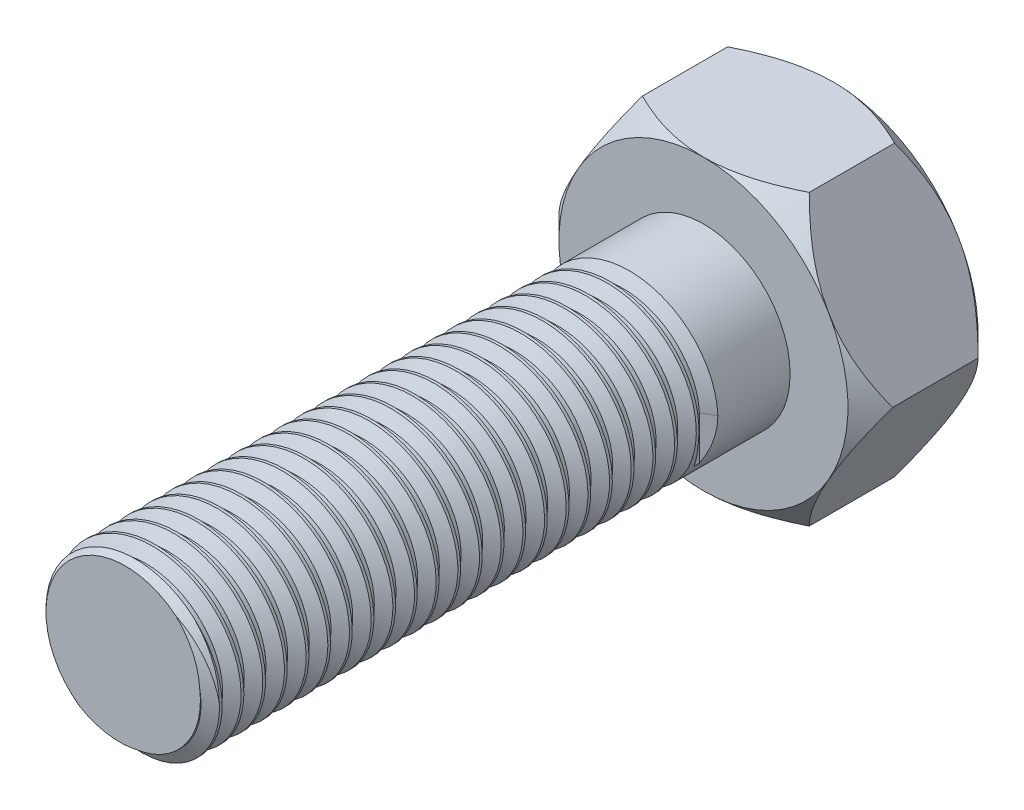
SolidWorks part; units mm, degrees
ref_plane "Front Plane" through (0, 0, 0) normal (0, 0, 1) x (1, 0, 0)
ref_plane "Top Plane" through (0, 0, 0) normal (0, 1, 0) x (1, 0, 0)
ref_plane "Right Plane" through (0, 0, 0) normal (1, 0, 0) x (0, 0, -1)
sketch "Sketch1" plane through (0, 0, 0) normal (0, 0, 1) x (1, 0, 0)
  line L1 (5.7735, -10) -> (11.547, 0)
  line L2 (11.547, 0) -> (5.7735, 10)
  line L3 (5.7735, 10) -> (-5.7735, 10)
  line L4 (-5.7735, 10) -> (-11.547, 0)
  line L5 (-11.547, 0) -> (-5.7735, -10)
  line L6 (-5.7735, -10) -> (5.7735, -10)
  circle A0 centre (0, 0) radius 10 construction
  point P1 (0, -10)
  dimension "D1" = 20
extrude "Boss-Extrude1" add sketch "Sketch1" along normal mid plane 9
sketch "Sketch3" plane through (0, 0, 4.5) normal (0, 0, 1) x (1, 0, 0)
  line L0 (-5.7735, 10) -> (-11.547, 0) construction
  circle A0 centre (0, 0) radius 10
extrude "Cut-Extrude1" cut sketch "Sketch3" against normal through all draft 45 flip side to cut
mirror "Mirror1" about plane through (0, 0, 0) normal (0, 0, 1) of "Cut-Extrude1"
sketch "Sketch4" plane through (0, 0, 4.5) normal (0, 0, 1) x (1, 0, 0)
  circle A0 centre (0, 0) radius 6
  dimension "D1" = 12
extrude "Boss-Extrude2" add sketch "Sketch4" along normal blind 40
chamfer "Chamfer1" distance 0.5 angle 45 1 edges at (6, 0, 44.5)
thread "Thread1" pitch 1.5 start angle 0, offset 5, length 0, pitch 1.5, diameter 12
ref_plane "Plane1" through (6, 0, 9.5) normal (0, -1, 0) x (1, 0, 0)
sketch "Thread Profile1" plane through (6, 0, 9.5) normal (0, -1, 0) x (1, 0, 0)
  line L0 (0, 0) -> (0, 1.5) construction
  line L11 (0, 0) -> (0, 1.3125)
  line L12 (0, 1.3125) -> (-0.8119, 0.8437)
  line L13 (-0.8119, 0.8437) -> (-0.8119, 0.4687)
  line L15 (-0.8119, 0.4687) -> (0, 0)
  line L17 (-0.8119, 0.6562) -> (0, 0.6562) construction
  point P2 (0, 0)
  dimension "Pitch" = 1.5
  dimension "Profile_Angle" = 60
  dimension "Profile_Land" = 0.375
  dimension "Profile_Height" = 0.8119
sketch "Sketch12" plane through (0, 0, 0) normal (0, 1, 0) x (1, 0, 0)
  line L4 (6, -9.5) -> (5.1881, -9.9687)
  line L5 (5.1881, -9.9687) -> (5.1881, -10.3437)
  line L6 (5.1881, -10.3437) -> (6, -10.8125)
  line L7 (6, -10.8125) -> (6, -9.5)
  line L8 (6, -9.5) -> (5.1881, -9.9687)
  line L9 (5.1881, -9.9687) -> (5.1881, -10.3437)
  line L10 (5.1881, -10.3437) -> (6, -10.8125)
  line L11 (6, -10.8125) -> (6, -9.5)
  dimension "D1" = 0
extrude "Cut-Extrude2" cut sketch "Sketch12" against normal through all
